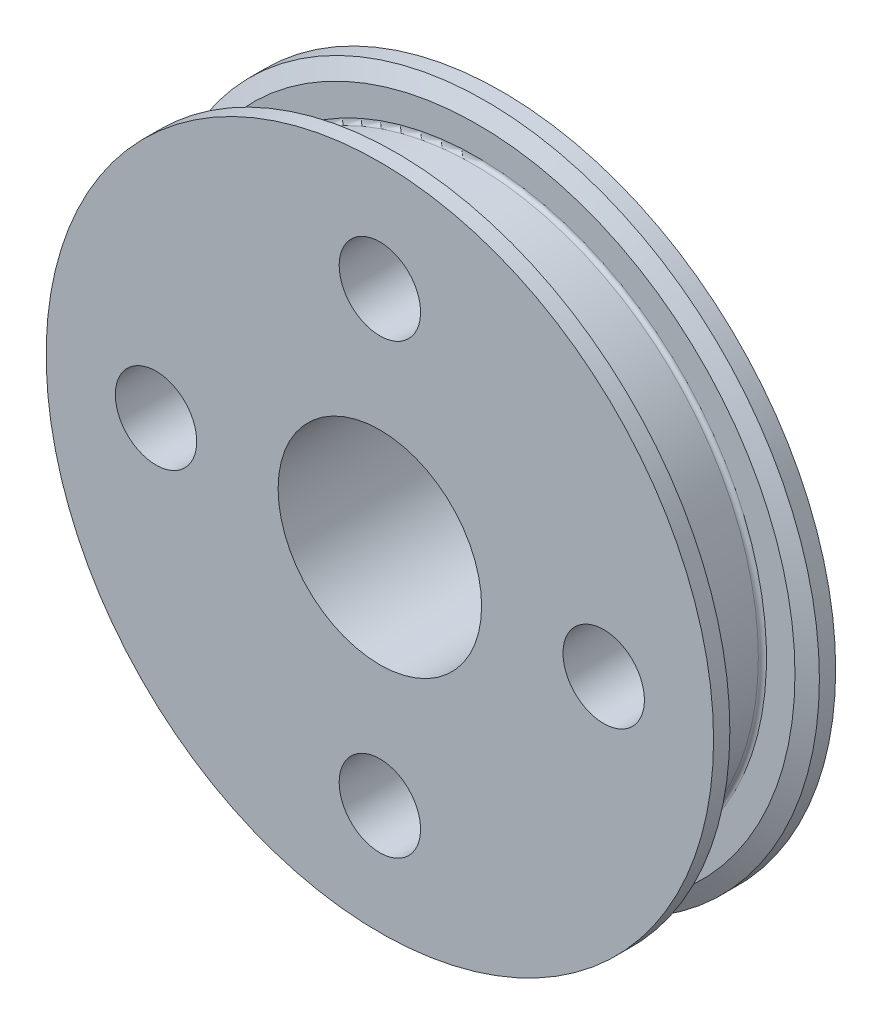
SolidWorks part; units mm, degrees
ref_plane "Front Plane" through (0, 0, 0) normal (0, 0, 1) x (1, 0, 0)
ref_plane "Top Plane" through (0, 0, 0) normal (0, 1, 0) x (1, 0, 0)
ref_plane "Right Plane" through (0, 0, 0) normal (1, 0, 0) x (0, 0, -1)
sketch "Sketch2" plane through (0, 0, 0) normal (1, 0, 0) x (0, 0, -1)
  line L0 (0, 6.35) -> (0, 20.828)
  line L1 (0, 20.828) -> (1.016, 20.828)
  line L2 (1.524, 19.812) -> (1.524, 17.78)
  line L3 (1.524, 17.78) -> (6.096, 17.78)
  line L4 (6.096, 17.78) -> (6.096, 19.812)
  line L5 (6.604, 20.828) -> (7.62, 20.828)
  line L6 (7.62, 20.828) -> (7.62, 6.35)
  line L8 (0, 6.35) -> (7.62, 6.35)
  line L9 (0, 6.35) -> (0, 0) construction
  line L10 (0, 0) -> (10.7816, 0) construction
  line L11 (6.096, 19.812) -> (6.604, 20.828)
  line L12 (1.016, 20.828) -> (1.524, 19.812)
  point P4 (1.524, 20.828)
  point P7 (6.096, 20.828)
  dimension "D1" = 17.78
  dimension "D2" = 7.62
  dimension "D3" = 3.048
  dimension "D4" = 6.35
  dimension "D5" = 4.572
  dimension "D6" = 1.016
  dimension "D7" = 0.508
  dimension "D8" = 0.508
  dimension "D9" = 1.016
revolve "Revolve1" add sketch "Sketch2" angle 360 about L10
sketch "Sketch3" plane through (0, 0, -7.62) normal (0, 0, -1) x (-1, 0, 0)
  line L1 (-9.525, -9.525) -> (9.525, -9.525)
  line L2 (-9.525, -9.525) -> (-9.525, 9.525)
  line L3 (-9.525, 9.525) -> (9.525, 9.525)
  line L4 (9.525, -9.525) -> (9.525, 9.525)
  circle A0 centre (0, 0) radius 6.35 construction
  circle A1 centre (0, 0) radius 6.35
  point P4 (9.525, 0)
  point P6 (0, 9.525)
  dimension "D1" = 19.05
extrude "Boss-Extrude1" add sketch "Sketch3" along normal blind 3.175
ref_plane "Plane1" through (0, 0, -3.81) normal (0, 0, -1) x (-1, 0, 0)
sketch "Sketch4" plane through (0, 0, -7.62) normal (0, 0, -1) x (-1, 0, 0)
  line L0 (0, 13.97) -> (0, 0) construction
  line L1 (0, 0) -> (0, -13.97) construction
  line L2 (-13.97, 0) -> (0, 0) construction
  line L3 (0, 0) -> (13.97, 0) construction
  circle A0 centre (0, 13.97) radius 2.54
  circle A1 centre (13.97, 0) radius 2.54
  circle A2 centre (0, -13.97) radius 2.54
  circle A3 centre (-13.97, 0) radius 2.54
  dimension "D1" = 5.08
  dimension "D2" = 13.97
extrude "Cut-Extrude1" cut sketch "Sketch4" against normal through all
fillet "Fillet1" radius 0.254 2 edges at (17.78, 0, -6.096) (17.78, 0, -1.524)
